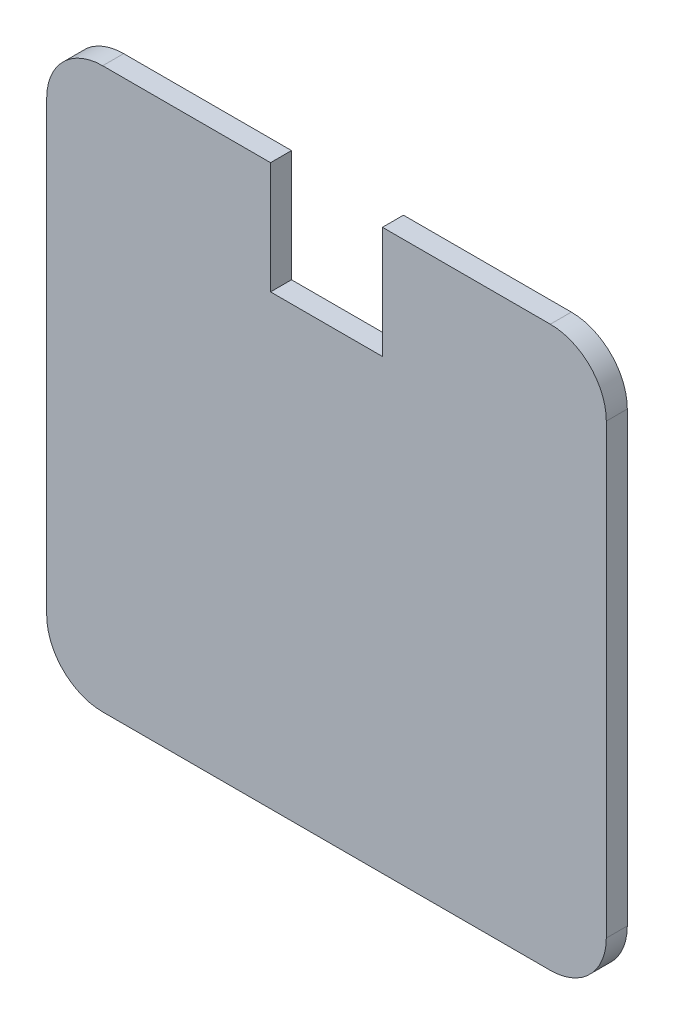
SolidWorks part; units mm, degrees
material "Polyurethane Foam Rigid"
ref_plane "Front Plane" through (0, 0, 0) normal (0, 0, 1) x (1, 0, 0)
ref_plane "Top Plane" through (0, 0, 0) normal (0, 1, 0) x (1, 0, 0)
ref_plane "Right Plane" through (0, 0, 0) normal (1, 0, 0) x (0, 0, -1)
sketch "Sketch1" plane through (0, 0, 0) normal (0, 0, 1) x (1, 0, 0)
  line L2 (-63.5, 50.8) -> (-63.5, -50.8)
  line L3 (-50.8, -63.5) -> (50.8, -63.5)
  line L4 (63.5, 50.8) -> (63.5, -50.8)
  line L5 (-12.7, 63.5) -> (12.7, 63.5) construction
  line L6 (-12.7, 63.5) -> (-12.7, 38.1)
  line L11 (50.8, 63.5) -> (12.7, 63.5)
  line L12 (-12.7, 63.5) -> (-50.8, 63.5)
  line L13 (0, 0) -> (0, 38.1) construction
  line L14 (-12.7, 38.1) -> (12.7, 38.1)
  line L15 (12.7, 38.1) -> (12.7, 63.5)
  line L16 (-59.7803, 59.7803) -> (59.7803, -59.7803) construction
  arc A0 (-63.5, -50.8) -> (-50.8, -63.5) centre (-50.8, -50.8) ccw
  arc A1 (50.8, -63.5) -> (63.5, -50.8) centre (50.8, -50.8) ccw
  arc A2 (63.5, 50.8) -> (50.8, 63.5) centre (50.8, 50.8) ccw
  arc A3 (-50.8, 63.5) -> (-63.5, 50.8) centre (-50.8, 50.8) ccw
  point P0 (0, 0)
  point P1 (0, 0)
  point P21 (59.7803, -59.7803)
  dimension "D3" = 12.7
  dimension "D1" = 127
  dimension "D5" = 25.4
  dimension "D2" = 25.4
  dimension "D4" = 127
extrude "Boss-Extrude1" add sketch "Sketch1" along normal blind 4.7625
equation "\"height\"= 8.875"
equation "\"span\"= 48"
equation "\"wing_chord\"= 9"
equation "\"fuse_len\"= 15"
equation "\"fuse_height\"= 5"
equation "\"fuse_wid\"= 5"
equation "\"D1@Sketch1\"=\"fuse_height\""
equation "\"D4@Sketch1\"=\"fuse_wid\""
